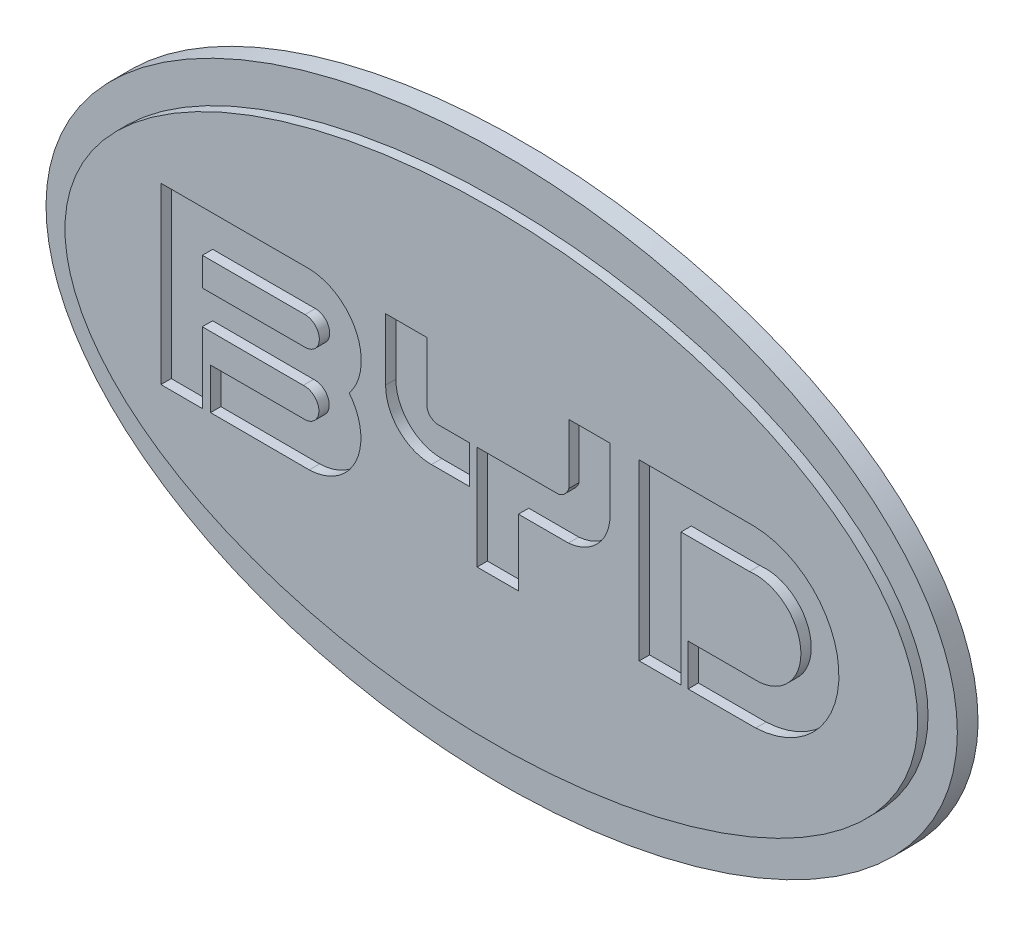
SolidWorks part; units mm, degrees
ref_plane "前视基准面" through (0, 0, 0) normal (0, 0, 1) x (1, 0, 0)
ref_plane "上视基准面" through (0, 0, 0) normal (0, 1, 0) x (1, 0, 0)
ref_plane "右视基准面" through (0, 0, 0) normal (1, 0, 0) x (0, 0, -1)
other "Configuration Table"
sketch "草图3" plane through (0, 0, 0) normal (0, 0, 1) x (1, 0, 0)
  line L0 (115.6969, 115.2379) -> (115.6986, 115.2379)
  line L2 (85.8579, 123.7017) -> (85.8579, 106.8315)
  line L3 (85.8579, 106.8315) -> (89.8579, 106.8213)
  line L4 (89.8579, 106.8213) -> (89.8579, 113.6772)
  line L5 (89.8579, 113.6772) -> (99.8624, 113.6516)
  line L6 (90.6564, 110.8641) -> (99.8624, 110.8641)
  line L7 (90.6564, 110.8641) -> (90.6564, 106.8799)
  line L8 (90.6564, 106.8799) -> (100.2082, 106.8555)
  line L9 (89.8657, 119.6669) -> (89.8657, 116.9237)
  line L10 (89.8657, 116.9237) -> (99.7982, 116.9237)
  line L11 (89.8657, 119.6669) -> (99.8234, 119.6669)
  line L12 (85.8579, 123.7017) -> (100.3205, 123.7017)
  line L15 (107.5959, 123.6424) -> (111.5883, 123.6424)
  line L16 (111.5883, 123.6424) -> (111.5883, 117.8987)
  line L17 (107.5959, 123.6424) -> (107.5959, 117.6534)
  line L18 (112.679, 116.8781) -> (115.6969, 116.8781)
  line L19 (115.6969, 116.8781) -> (115.6969, 113.2163)
  line L20 (115.6969, 113.2163) -> (112.0263, 113.2163)
  line L21 (125.2826, 113.2641) -> (120.444, 113.2641)
  line L22 (120.444, 113.2641) -> (120.444, 106.8341)
  line L23 (120.444, 106.8341) -> (116.4463, 106.8341)
  line L24 (116.4463, 106.8341) -> (116.4463, 116.8736)
  line L25 (116.4463, 116.8736) -> (124.377, 116.8781)
  line L26 (125.3192, 117.8478) -> (125.3192, 123.6476)
  line L27 (125.3192, 123.6476) -> (129.3203, 123.6476)
  line L28 (129.3203, 123.6476) -> (129.3203, 117.5226)
  line L29 (143.8224, 110.843) -> (136.862, 110.843)
  line L30 (136.862, 110.843) -> (136.862, 106.8253)
  line L31 (136.862, 106.8253) -> (143.4094, 106.8253)
  line L32 (143.8991, 119.6394) -> (136.1794, 119.6394)
  line L33 (136.1794, 119.6394) -> (136.1794, 106.8149)
  line L34 (136.1794, 106.8149) -> (132.1372, 106.8149)
  line L35 (132.1372, 106.8149) -> (132.1372, 123.6607)
  line L36 (132.1372, 123.6607) -> (143.3261, 123.6607)
  arc A0 (99.6219, 110.8641) -> (99.629, 113.6522) centre (99.7422, 112.2579) ccw
  arc A1 (99.7982, 116.9237) -> (99.7974, 119.6669) centre (99.8104, 118.2953) ccw
  arc A5 (107.5959, 117.6534) -> (112.0263, 113.2163) centre (111.9964, 117.6167) ccw
  arc A6 (111.5883, 117.8987) -> (112.679, 116.8781) centre (112.6985, 117.992) ccw
  arc A8 (124.5477, 113.2641) -> (129.3203, 117.5226) centre (124.9151, 117.6559) ccw
  arc A9 (143.8224, 110.843) -> (142.8048, 119.6394) centre (143.3519, 115.2456) ccw
  arc A12 (124.377, 116.8781) -> (125.3192, 117.8478) centre (123.9301, 118.255) ccw
  arc A16 (104.0708, 115.2379) -> (100.3205, 123.7017) centre (100.0483, 118.5183) ccw
  arc A17 (99.8602, 106.8564) -> (104.0708, 115.2379) centre (100.0474, 112.0108) ccw
  arc A18 (115.6969, 115.2354) -> (115.6986, 115.2379) centre (111.9964, 117.6167) ccw
  arc A19 (143.4094, 106.8253) -> (143.3261, 123.6607) centre (143.0327, 115.2413) ccw
  ellipse E0 centre (117.8248, 115.2379) end of major axis (73.7348, 115.2379) minor radius 26.4432
  ellipse E1 centre (117.8248, 115.2379) end of major axis (159.0808, 115.2379) minor radius 22.4008
extrude "凸台-拉伸1" add sketch "草图3" along normal blind 3 contours E0
extrude "切除-拉伸2" cut sketch "草图3<4>" against normal blind 1 from surface contours L8 A17 A16 L12 L2 L3 L4 L5 A0 L6 L7 A1 L10 L9 L11 | A6 L16 L15 L17 A5 L20 L19 L18 | A12 L25 L24 L23 L22 L21 A8 L28 L27 L26 | L31 A19 L36 L35 L34 L33 L32 A9 L29 L30 | E0 E1 region at (110.8377, 117.7917, 0) region at (95.166, 115.3711, 0) region at (122.72, 115.2334, 0) region at (148.0358, 115.2048, 0) region at (160.8865, 115.2946, 0) starting at face at (161.9149, 115.2379, 3)
sketch "草图3<4>" plane through (0, 0, 0) normal (0, 0, 1) x (1, 0, 0) same geometry as "草图3"
